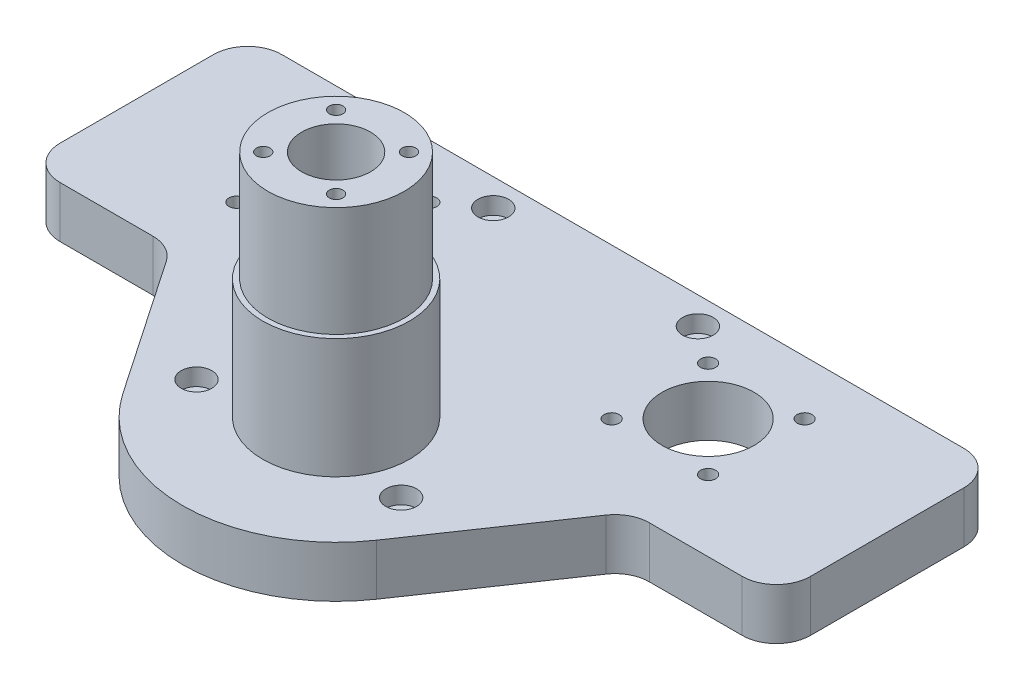
SolidWorks part; units mm, degrees
material "PLA Infill"
ref_plane "Front Plane" through (0, 0, 0) normal (0, 0, 1) x (1, 0, 0)
ref_plane "Top Plane" through (0, 0, 0) normal (0, 1, 0) x (1, 0, 0)
ref_plane "Right Plane" through (0, 0, 0) normal (1, 0, 0) x (0, 0, -1)
sketch "Sketch1" plane through (0, 0, 0) normal (0, 1, 0) x (1, 0, 0)
  line L0 (0, 0) -> (55, 54.0672) construction
  line L1 (55, 54.0672) -> (-55, 54.0672) construction
  line L2 (-55, 54.0672) -> (0, 0) construction
  line L3 (-79.7903, 37.1722) -> (-37.1854, -25.3425) construction
  line L4 (-55, 84.0672) -> (55, 84.0672)
  line L5 (37.1854, -25.3425) -> (79.7903, 37.1722) construction
  line L6 (-55, 84.0672) -> (-100, 84.0672)
  line L7 (-110, 74.0672) -> (-110, 29.0672)
  line L8 (-100, 19.0672) -> (-72.7378, 19.0672)
  line L9 (-64.4743, 14.6989) -> (-37.1854, -25.3425)
  line L10 (0, -1000) -> (0, 49000) construction
  line L11 (64.4743, 14.6989) -> (37.1854, -25.3425)
  line L12 (100, 19.0672) -> (72.7378, 19.0672)
  line L13 (110, 74.0672) -> (110, 29.0672)
  line L14 (55, 84.0672) -> (100, 84.0672)
  circle A0 centre (-55, 54.0672) radius 30 construction
  circle A1 centre (55, 54.0672) radius 30 construction
  circle A2 centre (0, 0) radius 45 construction
  arc A3 (-79.7903, 37.1722) -> (-55, 84.0672) centre (-55, 54.0672) cw construction
  arc A4 (55, 84.0672) -> (79.7903, 37.1722) centre (55, 54.0672) cw construction
  arc A5 (-37.1854, -25.3425) -> (37.1854, -25.3425) centre (0, 0) ccw
  arc A6 (-72.7378, 19.0672) -> (-64.4743, 14.6989) centre (-72.7378, 9.0672) cw
  arc A7 (-110, 29.0672) -> (-100, 19.0672) centre (-100, 29.0672) ccw
  arc A8 (-100, 84.0672) -> (-110, 74.0672) centre (-100, 74.0672) ccw
  arc A9 (72.7378, 19.0672) -> (64.4743, 14.6989) centre (72.7378, 9.0672) ccw
  arc A10 (110, 29.0672) -> (100, 19.0672) centre (100, 29.0672) cw
  arc A11 (100, 84.0672) -> (110, 74.0672) centre (100, 74.0672) cw
  point P23 (-67.4514, 19.0672)
  dimension "D3" = 60
  dimension "D4" = 90
  dimension "D5" = 10
  dimension "D6" = 55
  dimension "D1" = 110
  dimension "D2" = 77.125
  dimension "D7" = 35
extrude "Main Body" add sketch "Sketch1" along normal blind 15 contours A5 L11 A9 L12 A10 L13 A11 L14 L4 L6 A8 L7 A7 L8 A6 L9
sketch "Sketch3" plane through (0, 15, 0) normal (0, 1, 0) x (1, 0, 0)
  circle A0 centre (0, 0) radius 45 construction
  circle A1 centre (0, 0) radius 45 construction
  circle A2 centre (0, 0) radius 21.5
  dimension "D1" = 43
extrude "Front Extrusion" add sketch "Sketch3" along normal blind 67.3
sketch "Sketch4" plane through (0, 0, 0) normal (0, -1, 0) x (1, 0, 0)
  line L0 (0, -1000) -> (0, 49000) construction
  line L1 (-45, 0) -> (45, 0) construction
  line L2 (-85, -54.0672) -> (-25, -54.0672) construction
  line L3 (55, -54.0672) -> (-55, -54.0672) construction
  line L4 (-55, -24.0672) -> (-55, -84.0672) construction
  line L5 (-10.6773, 10.6773) -> (0, 0) construction
  line L6 (-10.6773, -10.6773) -> (0, 0) construction
  line L7 (-69.1421, -39.9251) -> (-55, -54.0672) construction
  line L8 (-100, -84.0672) -> (100, -84.0672) construction
  line L9 (100, -84.0672) -> (-100, -84.0672) construction
  line L10 (-30, -76.0672) -> (0, -76.0672) construction
  line L11 (-30, -76.0672) -> (-30, 10.9328) construction
  line L12 (-30, 10.9328) -> (0, 10.9328) construction
  line L13 (0, -76.0672) -> (0, 10.9328) construction
  circle A0 centre (55, -54.0672) radius 30 construction
  circle A1 centre (0, 0) radius 45 construction
  circle A2 centre (-55, -54.0672) radius 30 construction
  circle A3 centre (55, -54.0672) radius 30 construction
  circle A4 centre (0, 0) radius 45 construction
  circle A5 centre (-55, -54.0672) radius 30 construction
  circle A6 centre (0, 0) radius 10.1
  circle A7 centre (-55, -54.0672) radius 13.5
  circle A10 centre (-10.6773, 10.6773) radius 2
  circle A13 centre (-10.6773, -10.6773) radius 2
  circle A14 centre (-69.1421, -39.9251) radius 2.2
  circle A15 centre (-69.1421, -68.2094) radius 2.2
  circle A16 centre (-40.8579, -68.2094) radius 2.2
  circle A17 centre (-40.8579, -39.9251) radius 2.2
  circle A18 centre (55, -54.0672) radius 13.5
  circle A19 centre (69.1421, -68.2094) radius 2.2
  circle A20 centre (40.8579, -68.2094) radius 2.2
  circle A21 centre (40.8579, -39.9251) radius 2.2
  circle A22 centre (69.1421, -39.9251) radius 2.2
  circle A23 centre (10.6773, -10.6773) radius 2
  circle A24 centre (10.6773, 10.6773) radius 2
  circle A25 centre (-30, -76.0672) radius 2.5
  circle A26 centre (-30, 10.9328) radius 2.5
  circle A27 centre (30, -76.0672) radius 2.5
  circle A28 centre (30, 10.9328) radius 2.5
  dimension "D1" = 20.2
  dimension "D2" = 27
  dimension "D4" = 4
  dimension "D5" = 45
  dimension "D7" = 4.4
  dimension "D9" = 5
  dimension "D3" = 15.1
  dimension "D6" = 20
  dimension "D8" = 45
  dimension "D10" = 30
  dimension "D11" = 8
  dimension "D12" = 87
extrude "Bolt Holes" cut sketch "Sketch4" against normal through all
sketch "Sketch5" plane through (0, 0, 0) normal (0, -1, 0) x (1, 0, 0)
  line L0 (-14.92, 6.4347) -> (-9.9876, 1.5024)
  line L1 (-6.4347, 14.92) -> (-1.5024, 9.9876)
  line L2 (-10.6773, 10.6773) -> (0, 0) construction
  line L3 (-1000, 0) -> (49000, 0) construction
  line L4 (0, -1000) -> (0, 49000) construction
  line L5 (-14.92, -6.4347) -> (-9.9876, -1.5024)
  line L6 (-6.4347, -14.92) -> (-1.5024, -9.9876)
  line L7 (6.4347, -14.92) -> (1.5024, -9.9876)
  line L8 (14.92, -6.4347) -> (9.9876, -1.5024)
  line L9 (14.92, 6.4347) -> (9.9876, 1.5024)
  line L10 (6.4347, 14.92) -> (1.5024, 9.9876)
  circle A0 centre (-10.6773, 10.6773) radius 2 construction
  circle A1 centre (-10.6773, 10.6773) radius 6 construction
  circle A2 centre (0, 0) radius 10.1 construction
  arc A3 (-14.92, 6.4347) -> (-6.4347, 14.92) centre (-10.6773, 10.6773) cw
  circle A4 centre (0, 0) radius 10.1 construction
  arc A5 (-9.9876, 1.5024) -> (-1.5024, 9.9876) centre (0, 0) cw
  arc A6 (-14.92, -6.4347) -> (-6.4347, -14.92) centre (-10.6773, -10.6773) ccw
  arc A7 (-9.9876, -1.5024) -> (-1.5024, -9.9876) centre (0, 0) ccw
  arc A8 (14.92, -6.4347) -> (6.4347, -14.92) centre (10.6773, -10.6773) cw
  arc A9 (9.9876, -1.5024) -> (1.5024, -9.9876) centre (0, 0) cw
  arc A10 (14.92, 6.4347) -> (6.4347, 14.92) centre (10.6773, 10.6773) ccw
  arc A11 (9.9876, 1.5024) -> (1.5024, 9.9876) centre (0, 0) ccw
  dimension "D1" = 4
  dimension "D2" = 4
extrude "Bolt Recesses Rear" cut sketch "Sketch5" against normal blind 5
sketch "Sketch6" plane through (0, 15, 0) normal (0, 1, 0) x (1, 0, 0)
  circle A1 centre (30, 76.0672) radius 4.5
  circle A2 centre (-30, -10.9328) radius 2.5 construction
  circle A3 centre (30, -10.9328) radius 2.5 construction
  circle A4 centre (30, 76.0672) radius 2.5 construction
  circle A5 centre (-30, 76.0672) radius 2.5 construction
  circle A6 centre (-30, -10.9328) radius 2.5 construction
  circle A7 centre (30, -10.9328) radius 2.5 construction
  circle A8 centre (30, 76.0672) radius 2.5 construction
  circle A9 centre (-30, 76.0672) radius 2.5 construction
  circle A10 centre (-30, 76.0672) radius 4.5
  circle A11 centre (-30, -10.9328) radius 4.5
  circle A12 centre (30, -10.9328) radius 4.5
  dimension "D1" = 9
extrude "Bolt Recesses Front" cut sketch "Sketch6" against normal blind 5
ref_plane "First Bearing Section" through (0, 50.1, 0) normal (0, 1, 0) x (1, 0, 0)
sketch "Sketch7" plane through (0, 82.3, 0) normal (0, 1, 0) x (1, 0, 0)
  circle A0 centre (0, 0) radius 21.5 construction
  circle A1 centre (0, 0) radius 21.5
  circle A2 centre (0, 0) radius 20
  dimension "D1" = 40
extrude "Cut-Extrude1" cut sketch "Sketch7" against normal up to surface (32.2 mm away) up to plane "First Bearing Section"
sketch "Sketch8" plane through (0, 0, 0) normal (0, -1, 0) x (1, 0, 0)
  line L0 (0, -1000) -> (0, 49000) construction
  circle A0 centre (-69.1421, -68.2094) radius 2.2 construction
  circle A1 centre (-40.8579, -68.2094) radius 2.2 construction
  circle A2 centre (-40.8579, -39.9251) radius 2.2 construction
  circle A3 centre (-69.1421, -39.9251) radius 2.2 construction
  circle A4 centre (-69.1421, -68.2094) radius 2.2 construction
  circle A5 centre (-40.8579, -68.2094) radius 2.2 construction
  circle A6 centre (-40.8579, -39.9251) radius 2.2 construction
  circle A7 centre (-69.1421, -39.9251) radius 2.2 construction
  circle A8 centre (-69.1421, -39.9251) radius 3.5
  circle A9 centre (-40.8579, -39.9251) radius 3.5
  circle A10 centre (-40.8579, -68.2094) radius 3.5
  circle A11 centre (-69.1421, -68.2094) radius 3.5
  circle A12 centre (40.8579, -68.2094) radius 3.5
  circle A13 centre (40.8579, -39.9251) radius 3.5
  circle A14 centre (69.1421, -68.2094) radius 3.5
  circle A15 centre (69.1421, -39.9251) radius 3.5
  dimension "D1" = 7
extrude "Motor bolt head recesses" cut sketch "Sketch8" against normal blind 7
sketch "Sketch9" plane through (0, 0, 0) normal (0, -1, 0) x (1, 0, 0)
  line L0 (0, -1000) -> (0, 49000) construction
  line L1 (-110, -74.0672) -> (-110, -29.0672) construction
  line L2 (100, -84.0672) -> (-100, -84.0672) construction
  line L4 (-106, -74.0672) -> (-44, -74.0672) construction
  line L5 (-106, -74.0672) -> (-106, -32.0672) construction
  line L6 (-106, -32.0672) -> (-44, -32.0672) construction
  line L7 (-44, -74.0672) -> (-44, -32.0672) construction
  circle A0 centre (-106, -74.0672) radius 2
  circle A1 centre (-106, -32.0672) radius 2
  circle A2 centre (-44, -32.0672) radius 2
  circle A3 centre (-44, -74.0672) radius 2
  circle A4 centre (44, -74.0672) radius 2
  circle A5 centre (106, -74.0672) radius 2
  circle A6 centre (44, -32.0672) radius 2
  circle A7 centre (106, -32.0672) radius 2
  dimension "D3" = 4
  dimension "D1" = 4
  dimension "D2" = 10
  dimension "D4" = 62
  dimension "D5" = 42
extrude "Heat-set insert holes" cut sketch "Sketch9" against normal blind 6
